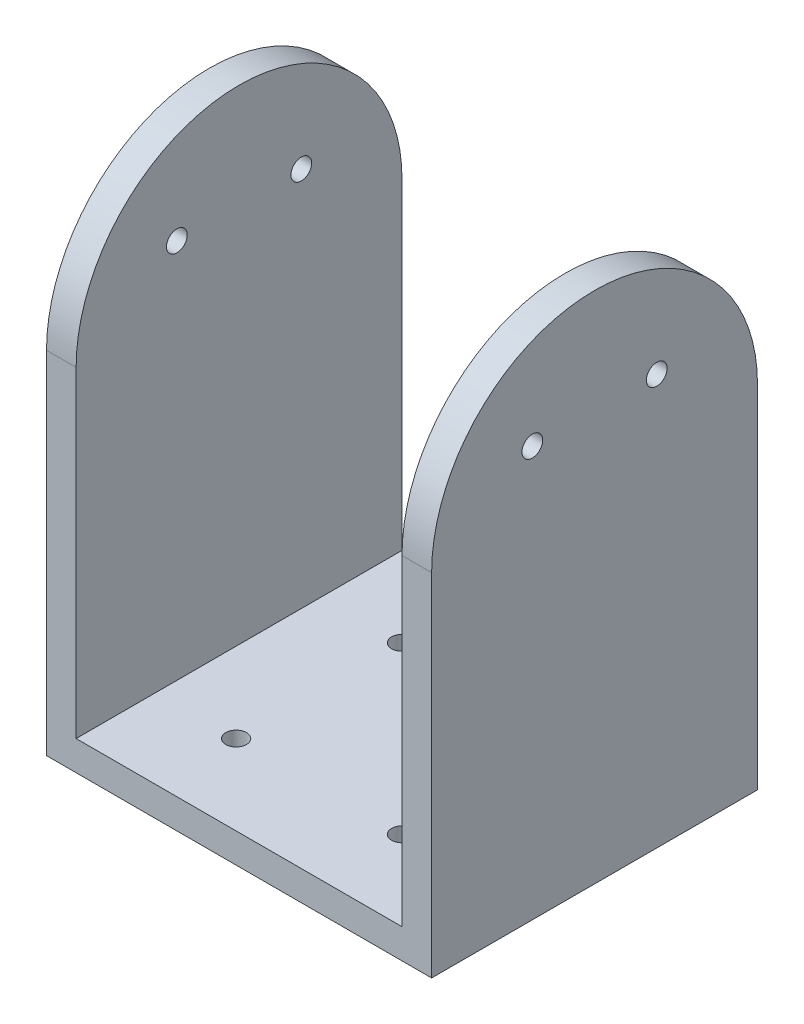
SolidWorks part; units mm, degrees
material "ABS"
ref_plane "Front Plane" through (0, 0, 0) normal (0, 0, 1) x (1, 0, 0)
ref_plane "Top Plane" through (0, 0, 0) normal (0, 1, 0) x (1, 0, 0)
ref_plane "Right Plane" through (0, 0, 0) normal (1, 0, 0) x (0, 0, -1)
sketch "Sketch1" plane through (0, 0, 0) normal (0, 1, 0) x (1, 0, 0)
  line L1 (-32.5, -27.5) -> (32.5, -27.5)
  line L2 (-32.5, -27.5) -> (-32.5, 27.5)
  line L3 (-32.5, 27.5) -> (32.5, 27.5)
  line L4 (32.5, -27.5) -> (32.5, 27.5)
  line L5 (-32.5, -27.5) -> (32.5, 27.5) construction
  line L6 (-32.5, 27.5) -> (32.5, -27.5) construction
  point P0 (0, 0)
  dimension "D1" = 55
  dimension "D2" = 65
extrude "Boss-Extrude1" add sketch "Sketch1" along normal blind 5
sketch "Sketch2" plane through (0, 5, 0) normal (0, 1, 0) x (1, 0, 0)
  line L0 (-32.5, -27.5) -> (32.5, -27.5) construction
  line L1 (-32.5, 27.5) -> (-27.5, 27.5)
  line L2 (-32.5, 27.5) -> (-32.5, -27.5)
  line L3 (-32.5, -27.5) -> (-27.5, -27.5)
  line L4 (-27.5, 27.5) -> (-27.5, -27.5)
  line L5 (0, -27.5) -> (0, 27.5) construction
  line L6 (32.5, 27.5) -> (-32.5, 27.5) construction
  line L7 (32.5, -27.5) -> (27.5, -27.5)
  line L8 (27.5, 27.5) -> (27.5, -27.5)
  line L9 (32.5, 27.5) -> (27.5, 27.5)
  line L10 (32.5, 27.5) -> (32.5, -27.5)
  point P13 (0, 0)
  dimension "D1" = 5
extrude "Boss-Extrude2" add sketch "Sketch2" along normal blind 81.75
sketch "Sketch3" plane through (-32.5, 0, 0) normal (-1, 0, 0) x (0, 0, 1)
  line L0 (0, 86.75) -> (0, 59.25) construction
  line L1 (-27.5, 86.75) -> (27.5, 86.75) construction
  line L2 (0, 59.25) -> (-27.5, 59.25) construction
  line L3 (-27.5, 86.75) -> (-27.5, 0) construction
  line L4 (27.5, 86.75) -> (27.5, 0) construction
  line L5 (-27.5, 86.75) -> (27.5, 86.75)
  line L6 (-27.5, 86.75) -> (-27.5, 59.25)
  line L7 (27.5, 59.25) -> (27.5, 86.75)
  arc A0 (-27.5, 59.25) -> (27.5, 59.25) centre (0, 59.25) cw
  circle A3 centre (-10.5, 69.25) radius 1.75
  circle A4 centre (10.5, 69.25) radius 1.75
  line M4 (27.5, 0) -> (27.5, 86.75)
  line M5 (27.5, 86.75) -> (-27.5, 86.75)
  line M6 (-27.5, 86.75) -> (-27.5, 0)
  dimension "D1" = 17.5
  dimension "D2" = 3.5
  dimension "D3" = 10.5
extrude "Cut-Extrude1" cut sketch "Sketch3" against normal up to next contours A0 L5 M6 | A0 M5 M4 | A3 | A4 region at (-32.5, 80.6074, 21.3574) region at (-32.5, 80.6074, -21.3574) region at (-32.5, 69.25, -10.5) region at (-32.5, 69.25, 10.5)
mirror "Mirror1" about plane through (0, 0, 0) normal (1, 0, 0) of "Cut-Extrude1"
sketch "Sketch4" plane through (0, 0, 0) normal (0, -1, 0) x (1, 0, 0)
  line L0 (-32.6529, 0) -> (32.6529, 0) construction
  line L1 (0, 0) -> (-23.3253, 23.3253) construction
  line L2 (0, 0) -> (-23.3253, -23.3253) construction
  line L3 (0, -29.1207) -> (0, 29.1207) construction
  line L4 (0, 0) -> (23.3253, -23.3253) construction
  line L5 (0, 0) -> (23.3253, 23.3253) construction
  circle A0 centre (-14, 14) radius 1.75
  circle A1 centre (-14, -14) radius 1.75
  circle A2 centre (14, -14) radius 1.75
  circle A3 centre (14, 14) radius 1.75
  point P12 (0, 0)
  dimension "D2" = 3.5
  dimension "D1" = 45
  dimension "D3" = 14
extrude "Cut-Extrude2" cut sketch "Sketch4" against normal up to next
